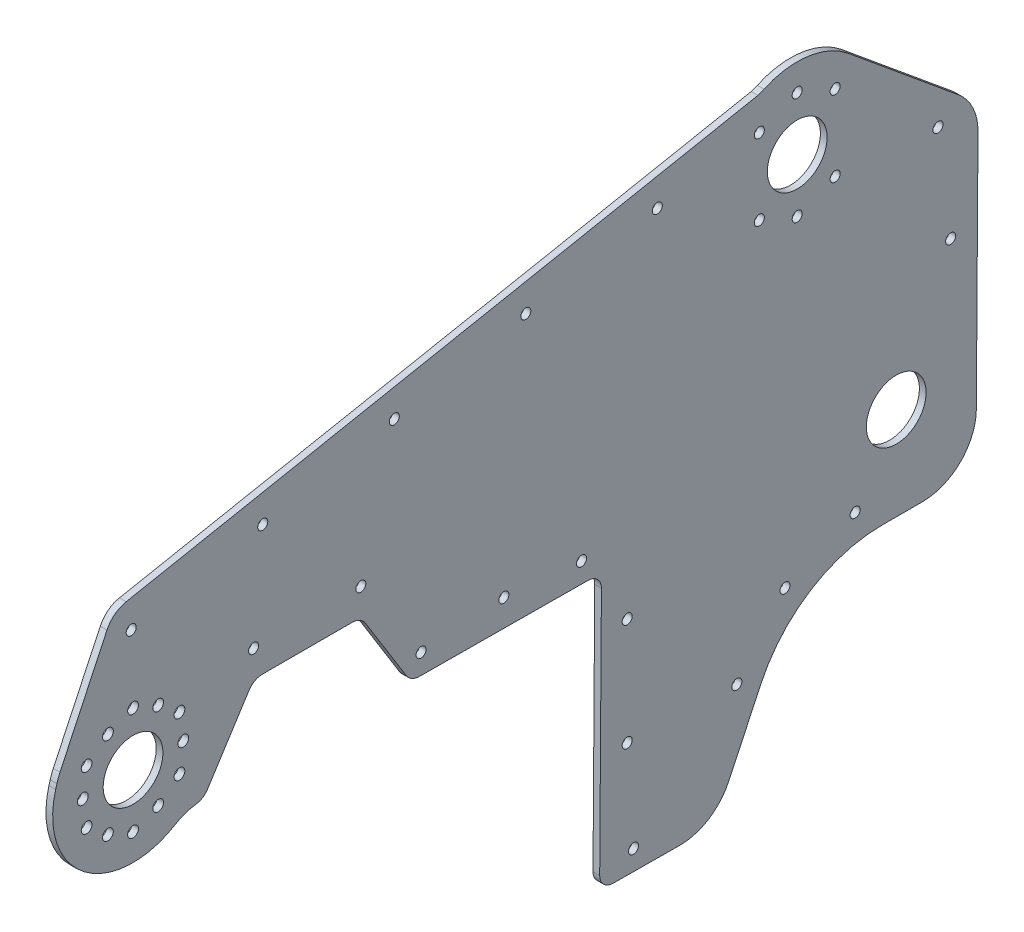
SolidWorks part; units mm, degrees
ref_plane "Front Plane" through (0, 0, 0) normal (0, 0, 1) x (1, 0, 0)
ref_plane "Top Plane" through (0, 0, 0) normal (0, 1, 0) x (1, 0, 0)
ref_plane "Right Plane" through (0, 0, 0) normal (1, 0, 0) x (0, 0, -1)
sketch "Sketch1" plane through (2085.2745, 0, 0) normal (-1, 0, 0) x (0, 0, 1)
  line L0 (-470.4626, 294.284) -> (-813.3543, 291.9025) construction
  line L1 (-819.6601, 285.5085) -> (-816.3083, -197.0799) construction
  line L2 (-816.3083, -197.0799) -> (-644.8624, -195.8891) construction
  line L3 (-638.5567, -189.4951) -> (-639.3726, -72.023) construction
  line L4 (-633.0668, -65.629) -> (-442.3722, -64.3046) construction
  line L5 (-380.6906, -25.2502) -> (-470.4626, 294.284) construction
  line L6 (-470.4626, 294.284) -> (-813.3543, 291.9025) construction
  line L7 (-819.6601, 285.5085) -> (-818.6898, 145.8119) construction
  line L8 (-676.4765, -196.1087) -> (-644.8624, -195.8891)
  line L9 (-638.5567, -189.4951) -> (-639.3726, -72.023)
  line L10 (-633.0668, -65.629) -> (-553.1901, -65.0743)
  line L11 (-380.6906, -25.2502) -> (-381.2742, -23.1727)
  line L12 (-406.6004, 23.1935) -> (-802.249, 140.9199) construction
  line L14 (-756.4363, 89.0125) -> (-808.6343, 45.9004)
  line L15 (-817.8587, 26.1401) -> (-817.0703, -87.3715)
  line L16 (-818.5707, 128.6591) -> (-817.9425, 38.2125) construction
  line L17 (-393.1787, 19.1998) -> (-470.4626, 294.284) construction
  line L18 (-699.6149, -181.5678) -> (-715.0401, -148.9488)
  line L19 (-772.4451, -112.5951) -> (-791.6709, -112.5951)
  line L20 (-816.8951, -112.5951) -> (-816.3083, -197.0799) construction
  line L21 (-816.3083, -197.0799) -> (-692.6854, -196.2212) construction
  line L22 (-530.97, 35.9025) -> (-713.5248, 93.2198) construction
  line L23 (-384.9948, -9.9298) -> (-389.3911, 5.7185) construction
  line L24 (-546.7673, -61.4706) -> (-527.5902, -30.5489)
  line L25 (-521.1144, -26.945) -> (-478.7266, -26.945)
  line L26 (-472.3074, -30.4591) -> (-452.7015, -61.1107)
  line L27 (-405.0283, 28.0353) -> (-382.753, -19.2109)
  line L28 (-475.9205, -39.5052) -> (-523.9205, -39.5052) construction
  line L29 (-475.9205, -39.5052) -> (-523.9205, -39.5052) construction
  line L30 (-548.9841, -65.045) -> (-450.6219, -64.3619) construction
  line L31 (-527.1657, 35.3193) -> (-416.5156, 35.3193) construction
  line L32 (-398.1188, -5.8092) -> (-529.1126, 35.3193) construction
  line L33 (-713.5248, 93.2198) -> (-414.0951, 35.0865)
  line L34 (-792.0032, 59.6366) -> (-540.5464, 59.6366) construction
  arc A0 (-813.3543, 291.9025) -> (-819.6601, 285.5085) centre (-813.3102, 285.5526) ccw construction
  arc A1 (-644.8624, -195.8891) -> (-638.5567, -189.4951) centre (-644.9065, -189.5392) ccw construction
  arc A2 (-633.0668, -65.629) -> (-639.3726, -72.023) centre (-633.0227, -71.9789) ccw construction
  arc A3 (-442.3722, -64.3046) -> (-380.6906, -25.2502) centre (-417.3705, -35.5552) ccw construction
  arc A4 (-813.3543, 291.9025) -> (-819.6601, 285.5085) centre (-813.3102, 285.5526) ccw construction
  arc A5 (-644.8624, -195.8891) -> (-638.5567, -189.4951) centre (-644.9065, -189.5392) ccw
  arc A6 (-633.0668, -65.629) -> (-639.3726, -72.023) centre (-633.0227, -71.9789) ccw
  arc A7 (-437.2155, -68.0789) -> (-380.6906, -25.2502) centre (-417.3705, -35.5552) ccw
  arc A8 (-406.6004, 23.1935) -> (-389.3911, 5.7185) centre (-413.8444, -1.1516) cw construction
  arc A11 (-715.0401, -148.9488) -> (-772.4451, -112.5951) centre (-772.4451, -176.0951) ccw
  arc A12 (-699.6149, -181.5678) -> (-676.4765, -196.1087) centre (-676.6529, -170.7093) ccw
  arc A13 (-791.6709, -112.5951) -> (-817.0703, -87.3715) centre (-791.6709, -87.1951) cw
  arc A14 (-802.249, 140.9199) -> (-818.5707, 128.6591) centre (-805.871, 128.7473) ccw construction
  circle A16 centre (-732.1738, 59.6366) radius 14.1605
  circle A17 centre (-779.0999, -68.5703) radius 14.1605
  circle A18 centre (-654.5854, -186.4314) radius 2.3812
  circle A19 centre (-629.9581, -56.0822) radius 2.3812
  circle A20 centre (-553.8955, -55.5539) radius 2.3812
  circle A21 centre (-417.3705, -35.5552) radius 14.1605
  arc A22 (-716.4192, 94.3267) -> (-756.4363, 89.0125) centre (-732.1738, 59.6366) ccw
  arc A23 (-382.753, -19.2109) -> (-381.2742, -23.1727) centre (-405.7275, -30.0428) cw
  arc A24 (-713.5248, 93.2198) -> (-716.4192, 94.3267) centre (-705.9161, 117.4534) cw
  arc A25 (-808.6343, 45.9004) -> (-817.8587, 26.1401) centre (-792.4593, 26.3165) ccw
  arc A26 (-447.2431, -64.564) -> (-437.2155, -68.0789) centre (-450.4455, -89.7613) cw
  arc A27 (-452.7015, -61.1107) -> (-447.2431, -64.564) centre (-446.2823, -57.0048) ccw
  arc A28 (-546.7673, -61.4706) -> (-553.1901, -65.0743) centre (-553.243, -57.4544) cw
  arc A29 (-478.7266, -26.945) -> (-472.3074, -30.4591) centre (-478.7266, -34.565) cw
  arc A30 (-527.5902, -30.5489) -> (-521.1144, -26.945) centre (-521.1144, -34.565) cw
  arc A31 (-398.1188, -5.8092) -> (-382.753, -19.2109) centre (-405.7275, -30.0428) cw construction
  arc A32 (-527.1657, 35.3193) -> (-530.97, 35.9025) centre (-527.1657, 48.0193) cw construction
  arc A33 (-414.0951, 35.0865) -> (-405.0283, 28.0353) centre (-416.5156, 22.6193) cw
  arc A34 (-416.5156, 35.3193) -> (-414.0951, 35.0865) centre (-416.5156, 22.6193) cw construction
  point P63 (-715.1948, 93.7441)
  point P77 (-499.9205, -26.945)
  point P78 (-499.9205, -39.5052)
  point P87 (-474.5551, -26.945)
  point P90 (-525.3551, -26.945)
  point P96 (-408.4626, 35.3193)
  dimension "D5" = 25.4
  dimension "D8" = 63.5
  dimension "D10" = 25.4
  dimension "D3" = 12.7
  dimension "D4" = 28.321
  dimension "D11" = 38.1
  dimension "D15" = 25.4
  dimension "D16" = 25.4
  dimension "D19" = 7.62
  dimension "D22" = 12.7
  dimension "D23" = 4.7625
  dimension "D1" = 44.45
  dimension "D2" = 146.05
  dimension "D6" = 44.45
  dimension "D7" = 38.1
  dimension "D9" = 76.2
  dimension "D12" = 50.8
  dimension "D13" = 330.2
  dimension "D14" = 53.975
  dimension "D17" = 50.8
  dimension "D18" = 38.1
  dimension "D20" = 60.287
  dimension "D21" = 120.65
  dimension "D24" = 172.2317
  dimension "D25" = 136.525
  dimension "D26" = 69.9712
  dimension "D27" = 126.23
extrude "Boss-Extrude2" add sketch "Sketch1" along normal blind 3.175
sketch "Sketch2" plane through (2085.2745, 0, 0) normal (1, 0, 0) x (0, 0, -1)
  circle A0 centre (732.1738, 59.6366) radius 14.1605 construction
  circle A1 centre (732.1738, 59.6366) radius 14.1605 construction
  circle A2 centre (732.1738, 85.0366) radius 2.3812
  circle A3 centre (732.1738, 34.2366) radius 2.3812
  circle A4 centre (750.1343, 41.676) radius 2.3812
  circle A5 centre (714.2134, 77.5972) radius 2.3812
  circle A6 centre (732.1738, 59.6366) radius 25.4 construction
  circle A7 centre (750.1343, 77.5972) radius 2.3812
  circle A8 centre (714.2134, 41.676) radius 2.3812
  dimension "D1" = 50.8
  dimension "D2" = 4.7625
  dimension "D3" = 7.4394
  dimension "D4" = 7.4394
extrude "Cut-Extrude1" cut sketch "Sketch2" against normal through all
sketch "Sketch3" plane through (2085.2745, 0, 0) normal (1, 0, 0) x (0, 0, -1)
  circle A1 centre (759.6181, -100.9825) radius 2.3813
  circle A2 centre (759.6181, -100.9825) radius 2.3813
  circle A3 centre (541.1877, 46.532) radius 2.3813
  circle A4 centre (541.1877, 46.532) radius 2.3812
  circle A5 centre (478.8516, 34.4297) radius 2.3813
  circle A6 centre (478.8516, 34.4297) radius 2.3813
  circle A7 centre (416.5156, 22.3274) radius 2.3813
  circle A8 centre (416.5156, 22.3274) radius 2.3813
  circle A9 centre (525.3205, -14.245) radius 2.3813
  circle A10 centre (525.3205, -14.245) radius 2.3813
  circle A11 centre (798.8869, 37.4794) radius 2.3813
  circle A12 centre (798.8869, 37.4794) radius 2.3813
  circle A13 centre (665.8598, 70.7367) radius 2.3813
  circle A14 centre (665.8598, 70.7367) radius 2.3812
  circle A15 centre (603.5237, 58.6344) radius 2.3813
  circle A16 centre (603.5237, 58.6344) radius 2.3812
  circle A17 centre (703.5591, -143.5195) radius 2.3813
  circle A18 centre (703.5591, -143.5195) radius 2.3813
  circle A19 centre (726.3842, -115.3922) radius 2.3813
  circle A20 centre (726.3842, -115.3922) radius 2.3813
  circle A21 centre (804.8987, -11.2496) radius 2.3813
  circle A22 centre (804.8987, -11.2496) radius 2.3813
  circle A23 centre (474.5205, -14.245) radius 2.3813
  circle A24 centre (474.5205, -14.245) radius 2.3813
  circle A25 centre (651.59, -141.5513) radius 2.3813
  circle A26 centre (651.59, -141.5513) radius 2.3813
  circle A27 centre (651.59, -90.7513) radius 2.3813
  circle A28 centre (651.59, -90.7513) radius 2.3813
  circle A29 centre (593.1285, -52.6513) radius 2.3813
  circle A30 centre (593.1285, -52.6513) radius 2.3813
  dimension "D1" = 0
  dimension "D2" = 0
  dimension "D3" = 0
  dimension "D4" = 0
  dimension "D5" = 0
  dimension "D6" = 0
  dimension "D7" = 0
  dimension "D8" = 0
  dimension "D9" = 0
  dimension "D10" = 0
  dimension "D11" = 0
  dimension "D12" = 0
  dimension "D13" = 0
  dimension "D14" = 0
  dimension "D15" = 0
extrude "Cut-Extrude2" cut sketch "Sketch3" against normal up to surface (3.175 mm away) up to face at (2082.0995, 85.0366, -734.5551)
sketch "Sketch4" plane through (2085.2745, 0, 0) normal (1, 0, 0) x (0, 0, -1)
  circle A0 centre (417.3705, -35.5552) radius 14.1605 construction
  circle A1 centre (417.3705, -35.5552) radius 14.1605 construction
sketch "Sketch5" plane through (2085.2745, 0, 0) normal (1, 0, 0) x (0, 0, -1)
  line L0 (-4.7879, -2.7643) -> (0, -5.5286)
  line L1 (0, -5.5286) -> (4.7879, -2.7643)
  line L2 (4.7879, -2.7643) -> (4.7879, 2.7643)
  line L3 (4.7879, 2.7643) -> (0, 5.5286)
  line L4 (0, 5.5286) -> (-4.7879, 2.7643)
  line L5 (-4.7879, 2.7643) -> (-4.7879, -2.7643)
  circle A0 centre (-11.9062, 20.6222) radius 2.5527
  circle A1 centre (0, 25.4) radius 2.5527
  circle A2 centre (-23.8125, 0) radius 2.5527
  circle A3 centre (-21.997, 12.7) radius 2.5527
  circle A4 centre (-11.9062, -20.6222) radius 2.5527
  circle A5 centre (-21.997, -12.7) radius 2.5527
  circle A6 centre (11.9062, -20.6222) radius 2.5527
  circle A7 centre (0, -25.4) radius 2.5527
  circle A8 centre (23.8125, 0) radius 2.5527
  circle A9 centre (21.997, -12.7) radius 2.5527
  circle A10 centre (11.9062, 20.6222) radius 2.5527
  circle A11 centre (21.997, 12.7) radius 2.5527
  circle A12 centre (0, 0) radius 30.1625
sketch "Sketch6" plane through (2085.2745, 0, 0) normal (1, 0, 0) x (0, 0, -1)
  line L0 (405.4643, -14.933) -> (393.558, -35.5552) construction
  line L1 (393.558, -35.5552) -> (405.4643, -56.1775) construction
  line L2 (405.4643, -56.1775) -> (429.2768, -56.1775) construction
  line L3 (429.2768, -56.1775) -> (441.183, -35.5552) construction
  line L4 (441.183, -35.5552) -> (429.2768, -14.933) construction
  line L5 (429.2768, -14.933) -> (405.4643, -14.933) construction
  line L6 (395.3735, -22.8552) -> (417.3705, -10.1552) construction
  line L7 (417.3705, -10.1552) -> (439.3675, -22.8552) construction
  line L8 (439.3675, -22.8552) -> (439.3675, -48.2552) construction
  line L9 (439.3675, -48.2552) -> (417.3705, -60.9552) construction
  line L10 (417.3705, -60.9552) -> (395.3735, -48.2552) construction
  line L11 (395.3735, -48.2552) -> (395.3735, -22.8552) construction
  circle A0 centre (417.3705, -35.5552) radius 23.8125 construction
  circle A1 centre (417.3705, -35.5552) radius 25.4 construction
  circle A2 centre (395.3735, -48.2552) radius 2.5527
  circle A3 centre (417.3705, -35.5552) radius 14.1605 construction
  circle A4 centre (405.4643, -56.1775) radius 2.5527
  circle A6 centre (395.3735, -22.8552) radius 2.5527
  circle A8 centre (393.558, -35.5552) radius 2.5527
  circle A10 centre (417.3705, -10.1552) radius 2.5527
  circle A12 centre (405.4643, -14.933) radius 2.5527
  circle A14 centre (439.3675, -22.8552) radius 2.5527
  circle A16 centre (429.2768, -14.933) radius 2.5527
  circle A18 centre (439.3675, -48.2552) radius 2.5527
  circle A20 centre (441.183, -35.5552) radius 2.5527
  circle A22 centre (417.3705, -60.9552) radius 2.5527
  circle A24 centre (429.2768, -56.1775) radius 2.5527
  dimension "D1" = 50.8
  dimension "D2" = 47.625
  dimension "D3" = 5.1054
extrude "Cut-Extrude3" cut sketch "Sketch6" against normal through all
